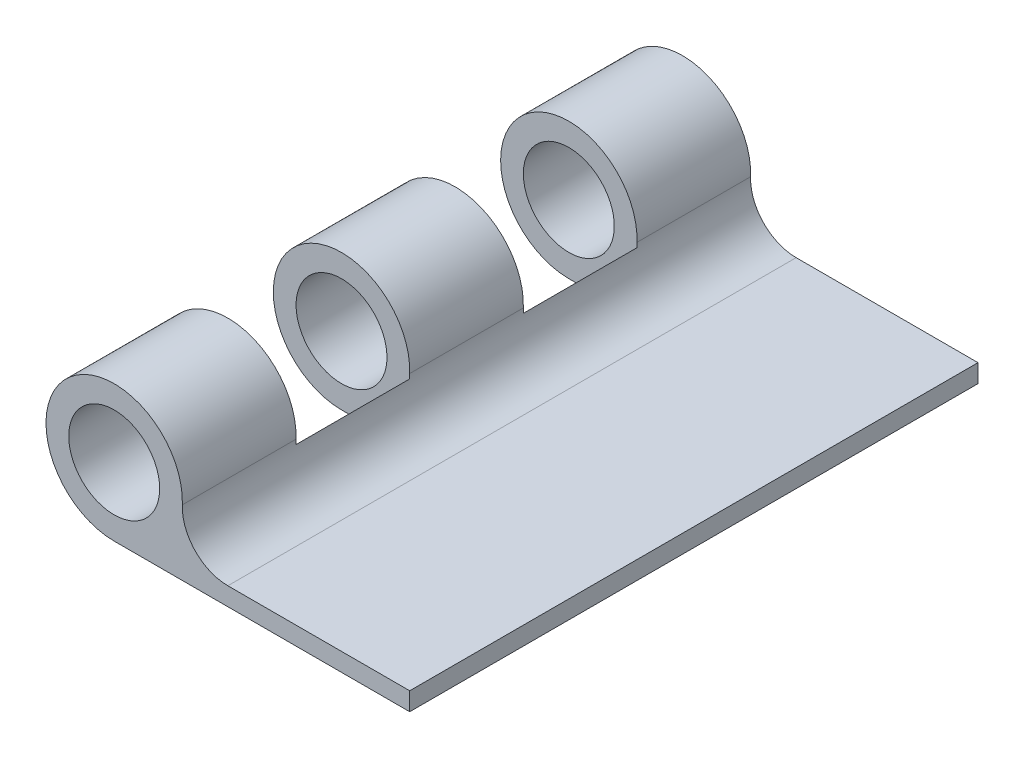
SolidWorks part; units mm, degrees
material "Aço cromo inoxidável"
ref_plane "Plano frontal" through (0, 0, 0) normal (0, 0, 1) x (1, 0, 0)
ref_plane "Plano superior" through (0, 0, 0) normal (0, 1, 0) x (1, 0, 0)
ref_plane "Plano direito" through (0, 0, 0) normal (1, 0, 0) x (0, 0, -1)
sketch "Esboço1" plane through (0, 0, 0) normal (0, 0, 1) x (1, 0, 0)
  line L0 (0, 0) -> (-13, 0)
  line L2 (-8, 0.8) -> (0, 0.8)
  line L3 (0, 0.8) -> (0, 0)
  arc A0 (-13, 0) -> (-12.9495, 5.9996) centre (-13, 3) cw
  arc A1 (-12.9495, 5.9996) -> (-10.0023, 2.8824) centre (-13, 3) cw
  arc A2 (-10.0023, 2.8824) -> (-8, 0.8) centre (-8, 2.8038) ccw
  circle A3 centre (-13, 3) radius 2
  dimension "D4" = 13
  dimension "D5" = 1
  dimension "D2" = 4
  dimension "D1" = 0.8
  dimension "D3" = 5
extrude "Ressalto-extrusão1" add sketch "Esboço1" along normal blind 25
sketch "Esboço2" plane through (0, 0, 0) normal (0, -1, 0) x (1, 0, 0)
  line L0 (-16, 25) -> (-16, 0) construction
  line L1 (-16, 5) -> (-10, 5)
  line L2 (-16, 5) -> (-16, 10)
  line L3 (-16, 10) -> (-10, 10)
  line L4 (-10, 5) -> (-10, 10)
  line L7 (-16, 15) -> (-16, 20)
  line L8 (-16, 15) -> (-10, 15)
  line L9 (-10, 15) -> (-10, 20)
  line L10 (-16, 20) -> (-10, 20)
  line L11 (-16, 25) -> (-16, 30)
  line L12 (-16, 25) -> (-10, 25)
  line L13 (-10, 25) -> (-10, 30)
  line L14 (-16, 30) -> (-10, 30)
  line L15 (-16, 0) -> (-10, 0) construction
  point P10 (0, 0)
  point P19 (0, 0)
  point P20 (0, 0)
  dimension "D1" = 5
  dimension "D2" = 3
  dimension "D3" = 5
  dimension "D4" = 5
  dimension "D5" = 6
extrude "Corte-extrusão1" cut sketch "Esboço2" against normal through all
